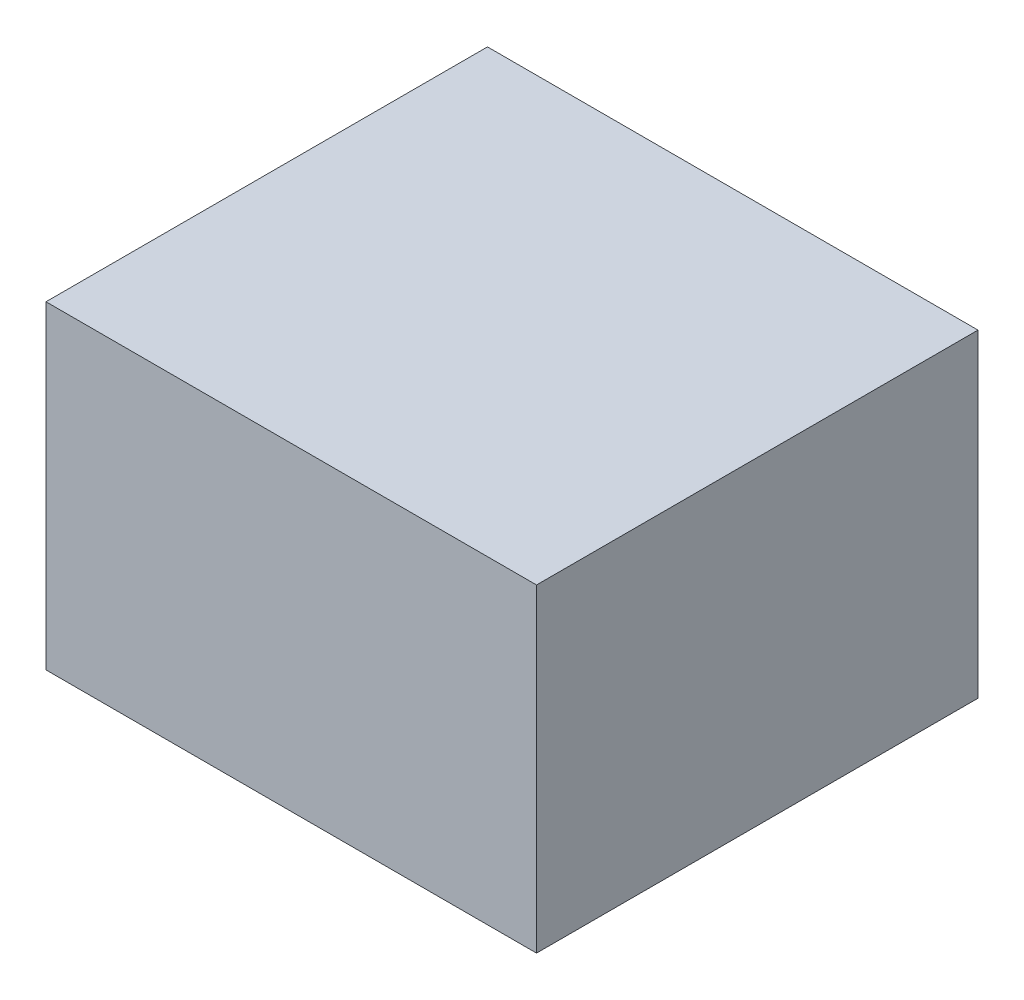
SolidWorks part; units mm, degrees
ref_plane "Front Plane" through (0, 0, 0) normal (0, 0, 1) x (1, 0, 0)
ref_plane "Top Plane" through (0, 0, 0) normal (0, 1, 0) x (1, 0, 0)
ref_plane "Right Plane" through (0, 0, 0) normal (1, 0, 0) x (0, 0, -1)
sketch "Sketch1" plane through (0, 0, 0) normal (0, 1, 0) x (1, 0, 0)
  line L1 (-100, -90) -> (100, -90)
  line L2 (-100, -90) -> (-100, 90)
  line L3 (-100, 90) -> (100, 90)
  line L4 (100, -90) -> (100, 90)
  line L5 (-100, -90) -> (100, 90) construction
  line L6 (-100, 90) -> (100, -90) construction
  point P0 (0, 0)
  dimension "D1" = 180
  dimension "D2" = 200
extrude "Boss-Extrude1" add sketch "Sketch1" along normal blind 130
